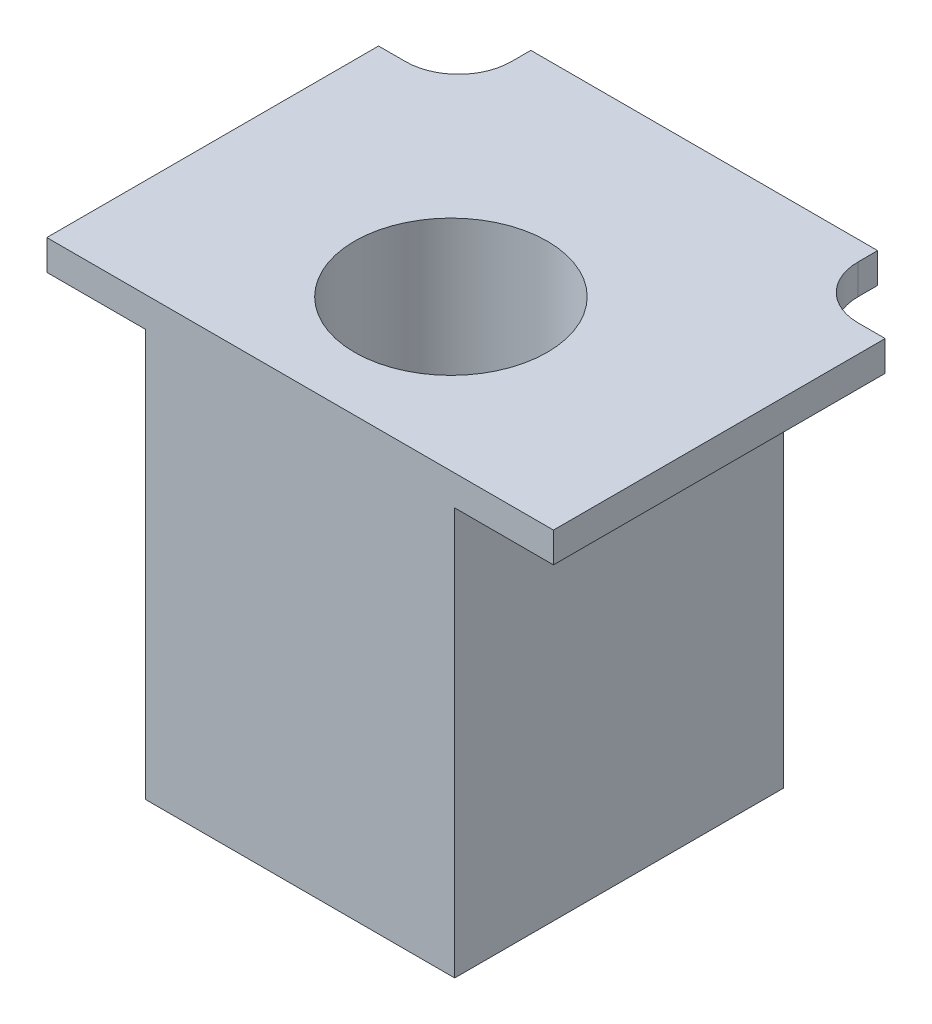
SolidWorks part; units mm, degrees
ref_plane "Front Plane" through (0, 0, 0) normal (0, 0, 1) x (1, 0, 0)
ref_plane "Top Plane" through (0, 0, 0) normal (0, 1, 0) x (1, 0, 0)
ref_plane "Right Plane" through (0, 0, 0) normal (1, 0, 0) x (0, 0, -1)
sketch "Sketch1" plane through (0, 0, 0) normal (0, 1, 0) x (1, 0, 0)
  line L1 (-5.125, 5.45) -> (5.125, 5.45)
  line L2 (-5.125, 5.45) -> (-5.125, -5.45)
  line L3 (-5.125, -5.45) -> (5.125, -5.45)
  line L4 (5.125, 5.45) -> (5.125, -5.45)
  line L5 (-5.125, 5.45) -> (5.125, -5.45) construction
  line L6 (-5.125, -5.45) -> (5.125, 5.45) construction
  point P0 (0, 0)
  dimension "D1" = 10.9
  dimension "D2" = 10.25
extrude "Boss-Extrude1" add sketch "Sketch1" along normal blind 1.5
sketch "Sketch2" plane through (0, 1.5, 0) normal (0, 1, 0) x (1, 0, 0)
  line L0 (-5.125, -5.45) -> (5.125, -5.45) construction
  line L5 (5.125, 5.45) -> (-5.125, 5.45) construction
  line L6 (-3.195, 3.75) -> (3.195, 3.75)
  line L7 (5.125, -5.45) -> (5.125, 5.45) construction
  line L8 (-5.125, 5.45) -> (-5.125, -5.45) construction
  line L11 (-3.195, 3.75) -> (-3.195, -4.65)
  line L12 (-3.195, -4.65) -> (3.195, -4.65)
  line L13 (3.195, 3.75) -> (3.195, -4.65)
  dimension "D1" = 1.7
  dimension "D2" = 0.8
  dimension "D3" = 1.93
  dimension "D4" = 1.93
extrude "Cut-Extrude1" cut sketch "Sketch2" against normal through all
sketch "Sketch3" plane through (0, 1.5, 0) normal (0, 1, 0) x (1, 0, 0)
  line L1 (-5.125, 5.45) -> (5.125, 5.45)
  line L2 (-5.125, 5.45) -> (-5.125, -5.45)
  line L3 (-5.125, -5.45) -> (5.125, -5.45)
  line L4 (5.125, 5.45) -> (5.125, -5.45)
  circle A0 centre (0, -0.45) radius 3.195
  dimension "D1" = 6.39
  dimension "D2" = 5.9
extrude "Boss-Extrude2" add sketch "Sketch3" along normal blind 13
sketch "Sketch5" plane through (0, 14.5, 0) normal (0, 1, 0) x (1, 0, 0)
  line L5 (-5.125, -5.45) -> (5.125, -5.45) construction
  line L44 (-10, 9.55) -> (10, 9.55) construction
  line L49 (-10, 9.55) -> (-10, -5.45) construction
  line L50 (-10, -5.45) -> (10, -5.45) construction
  line L51 (10, 9.55) -> (10, -5.45) construction
  line L53 (0, -0.45) -> (-4, -0.45) construction
  line L54 (-9.12, 8.67) -> (9.12, 8.67) construction
  line L55 (-9.12, 8.67) -> (-9.12, -5.45) construction
  line L56 (-9.12, -5.45) -> (9.12, -5.45) construction
  line L57 (9.12, 8.67) -> (9.12, -5.45) construction
  line L58 (-8.4, 7.95) -> (8.4, 7.95) construction
  line L59 (-8.4, 7.95) -> (-8.4, -5.45) construction
  line L60 (-8.4, -5.45) -> (8.4, -5.45) construction
  line L61 (8.4, 7.95) -> (8.4, -5.45) construction
  line L62 (0, -0.45) -> (0, -4.45) construction
  line L63 (-5.75, 7.3) -> (-5.75, 7.95)
  line L64 (-7.5, 5.55) -> (-8.4, 5.55)
  line L65 (-8.4, 7.95) -> (-5.75, 7.95)
  line L66 (-8.4, 5.55) -> (-8.4, 7.95)
  line L67 (7.5, 5.55) -> (8.4, 5.55)
  line L68 (8.4, 5.55) -> (8.4, 7.95)
  line L69 (5.75, 7.3) -> (5.75, 7.95)
  line L70 (5.75, 7.95) -> (8.4, 7.95)
  line L71 (-8.4, 5.55) -> (-8.4, -5.45)
  line L72 (-8.4, -5.45) -> (8.4, -5.45)
  line L73 (8.4, -5.45) -> (8.4, 5.55)
  line L74 (-5.75, 7.95) -> (5.75, 7.95)
  circle A0 centre (-7.5, 7.3) radius 1.75 construction
  circle A1 centre (7.5, 7.3) radius 1.75 construction
  arc A4 (5.75, 7.3) -> (7.5, 5.55) centre (7.5, 7.3) ccw
  arc A5 (-7.5, 5.55) -> (-5.75, 7.3) centre (-7.5, 7.3) ccw
  point P10 (0, -0.45)
  line M9 (-5.125, 5.45) -> (-5.125, -5.45)
  line M11 (5.125, -5.45) -> (5.125, 5.45)
  line M12 (5.125, 5.45) -> (-5.125, 5.45)
  circle M13 centre (0, -0.45) radius 3.195
  dimension "D4" = 0.88
  dimension "D10" = 3.5
  dimension "D3" = 10
  dimension "D5" = 0.88
  dimension "D7" = 1.6
  dimension "D8" = 1.6
  dimension "D13" = 10
  dimension "D2" = 10
  dimension "D6" = 0.88
  dimension "D9" = 1.6
  dimension "D11" = 2.25
  dimension "D12" = 2.5
extrude "Boss-Extrude3" add sketch "Sketch5" against normal blind 1 contours M12 M13 M11 M9 region at (-5.5351, 14.5, -7.625)
